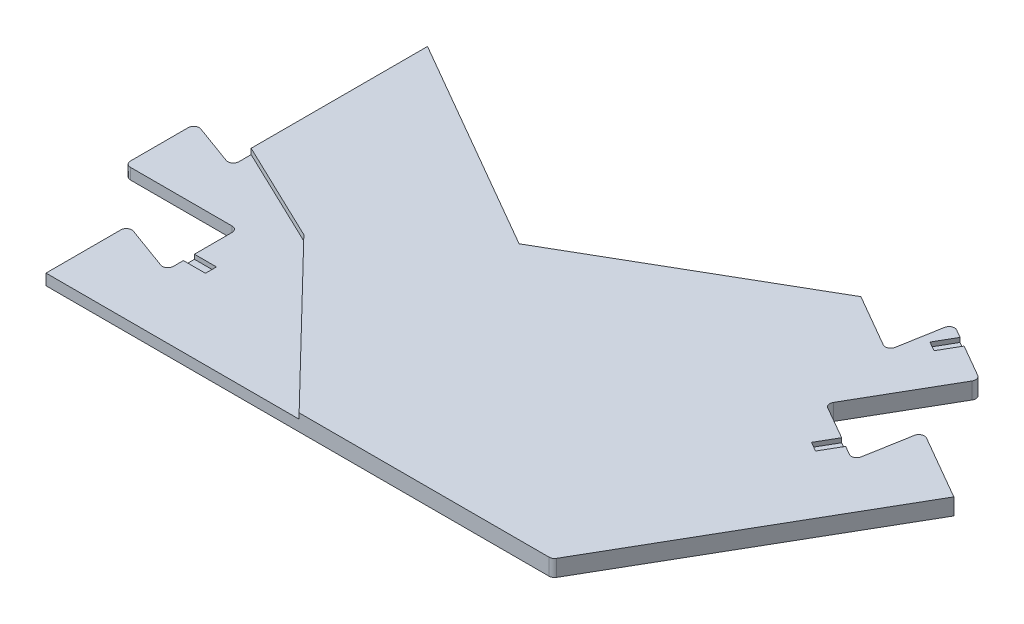
SolidWorks part; units mm, degrees
ref_plane "Přední rovina" through (0, 0, 0) normal (0, 0, 1) x (1, 0, 0)
ref_plane "Horní rovina" through (0, 0, 0) normal (0, 1, 0) x (1, 0, 0)
ref_plane "Pravá rovina" through (0, 0, 0) normal (1, 0, 0) x (0, 0, -1)
sketch "Skica1" plane through (0, 0, 0) normal (0, 1, 0) x (1, 0, 0)
  line L18 (13.6775, 53.6901) -> (26.6679, 46.1901)
  line L19 (26.6679, 46.1901) -> (0, 0)
  line L27 (-91.8562, 37.22) -> (-73.4914, 28.4198)
  line L34 (-91.8562, 0) -> (-91.8562, 15)
  line L36 (-91.8562, 15) -> (-81.3562, 11.1783)
  line L37 (-81.3562, 11.1783) -> (-81.3562, 24.2783)
  line L38 (-81.3562, 24.2783) -> (-101.8068, 24.2783)
  line L39 (-73.4914, 28.4198) -> (-45.9281, 0)
  line L44 (-91.8562, 0) -> (0, 0)
  line L45 (-91.8562, 33.5566) -> (-101.8068, 37.1783)
  line L46 (-101.8068, 37.1783) -> (-101.8068, 24.2783)
  line L47 (-91.8562, 69.22) -> (-91.8562, 33.5566)
  line L48 (-91.8562, 69.22) -> (-52.5387, 46.52)
  line L49 (-52.5387, 46.52) -> (-13.2211, 69.22)
  line L50 (13.6775, 53.6901) -> (11.7372, 42.686)
  line L51 (11.7372, 42.686) -> (0.3922, 49.236)
  line L52 (-13.2211, 69.22) -> (-2.393, 62.9684)
  line L53 (0.3922, 49.236) -> (10.6175, 66.9466)
  line L56 (-2.393, 62.9684) -> (-0.5543, 73.3966)
  line L57 (-0.5543, 73.3966) -> (10.6175, 66.9466)
  line L58 (-91.8562, 53.6901) -> (-91.8562, 1.8977) construction
  line L59 (-13.2211, 69.22) -> (26.6679, 46.1901) construction
  point P0 (0, 0)
  point P8 (-91.5815, 24.2783)
  point P23 (5.5048, 58.0913)
  dimension "D3" = 90
  dimension "D4" = 15
  dimension "D5" = 120
  dimension "D6" = 45.4
  dimension "D7" = 45.4
  dimension "D8" = 69.22
  dimension "D9" = 70
  dimension "D10" = 12.9
  dimension "D11" = 13.1
  dimension "D12" = 32
  dimension "D13" = 70
  dimension "D14" = 10.5
  dimension "D15" = 12.9
  dimension "D16" = 70
  dimension "D17" = 13.1
  dimension "D19" = 120
  dimension "D20" = 91.8562
  dimension "D21" = 10.5
  dimension "D22" = 15
  dimension "D23" = 69.22
  dimension "D24" = 120
  dimension "D25" = 20.3645
  dimension "D26" = 39.5906
extrude "Přidat vysunutím1" add sketch "Skica1" along normal blind 3 contours L57 L56 L52 L49 L48 L47 L27 L39 L44 L19 L18 L50 L51 L53 region at (-31.1142, 0, -34.1551)
extrude "Přidat vysunutím2" add sketch "Skica1<15>" along normal blind 2 contours L47 L58 L38 L37 L36 L34 L44 L39 L27 | L58 L45 L46 L38 region at (-76.8167, 0, -14.9585)
sketch "Skica1<15>" plane through (0, 0, 0) normal (0, 1, 0) x (1, 0, 0) same geometry as "Skica1"
fillet "Zaoblit1" radius 1 13 edges at (-81.3562, 1, -11.1783) (-91.8562, 1, -15) (-81.3562, 1, -24.2783) (-101.8068, 1, -24.2783) (-101.8068, 1, -37.1783) (-91.8562, 1, -33.5566) (0, 1.5, 0) (13.6775, 1.5, -53.6901) (11.7372, 1.5, -42.686) (0.3922, 1.5, -49.236) (-2.393, 1.5, -62.9684) (-0.5543, 1.5, -73.3966) (10.6175, 1.5, -66.9466)
sketch "Skica3" plane through (0, 2, 0) normal (0, 1, 0) x (1, 0, 0)
  line L3 (-81.3562, 17.7283) -> (-63.1221, 17.7283) construction
  line L9 (-81.3562, 11.1783) -> (-81.3562, 24.2783) construction
  line L10 (-73.4914, 28.4198) -> (-45.9281, 0) construction
  line L12 (-81.3562, 16.4283) -> (-77.3562, 16.4283)
  line L13 (-77.3562, 16.4283) -> (-77.3562, 14.4283)
  line L14 (-77.3562, 14.4283) -> (-81.3562, 14.4283)
  line L15 (-81.3562, 14.4283) -> (-81.3562, 16.4283)
  dimension "D1" = 4
  dimension "D2" = 2
  dimension "D3" = 1.3
extrude "Odebrat vysunutím1" cut sketch "Skica3" against normal blind 0.8
sketch "Skica4" plane through (0, 3, 0) normal (0, 1, 0) x (1, 0, 0)
  line L0 (5.0316, 70.1716) -> (-23.9536, 19.9677) construction
  line L1 (0.3922, 49.236) -> (10.6175, 66.9466) construction
  line L7 (-0.5543, 73.3966) -> (10.6175, 66.9466) construction
  line L8 (6.0647, 45.961) -> (-22.9206, -4.243) construction
  line L9 (7.1905, 45.311) -> (5.1905, 41.8469)
  line L10 (5.1905, 41.8469) -> (6.9226, 40.8469)
  line L11 (6.9226, 40.8469) -> (8.9226, 44.311)
  line L12 (8.9226, 44.311) -> (7.1905, 45.311)
  line L13 (11.7372, 42.686) -> (0.3922, 49.236) construction
  line L14 (0.1737, 68.3575) -> (2.1737, 71.8216)
  line L15 (1.9058, 67.3575) -> (0.1737, 68.3575)
  line L16 (3.9058, 70.8216) -> (1.9058, 67.3575)
  line L17 (2.1737, 71.8216) -> (3.9058, 70.8216)
  point P10 (5.0316, 70.1716)
  point P17 (16.3777, 67.7076)
  point P18 (6.0647, 45.961)
  point P19 (0, 0)
  point P22 (0, 0)
  dimension "D1" = 2
  dimension "D2" = 4
  dimension "D3" = 1.3
  dimension "D4" = 2
  dimension "D5" = 4
  dimension "D6" = 1.3
extrude "Odebrat vysunutím2" cut sketch "Skica4" against normal blind 0.8
